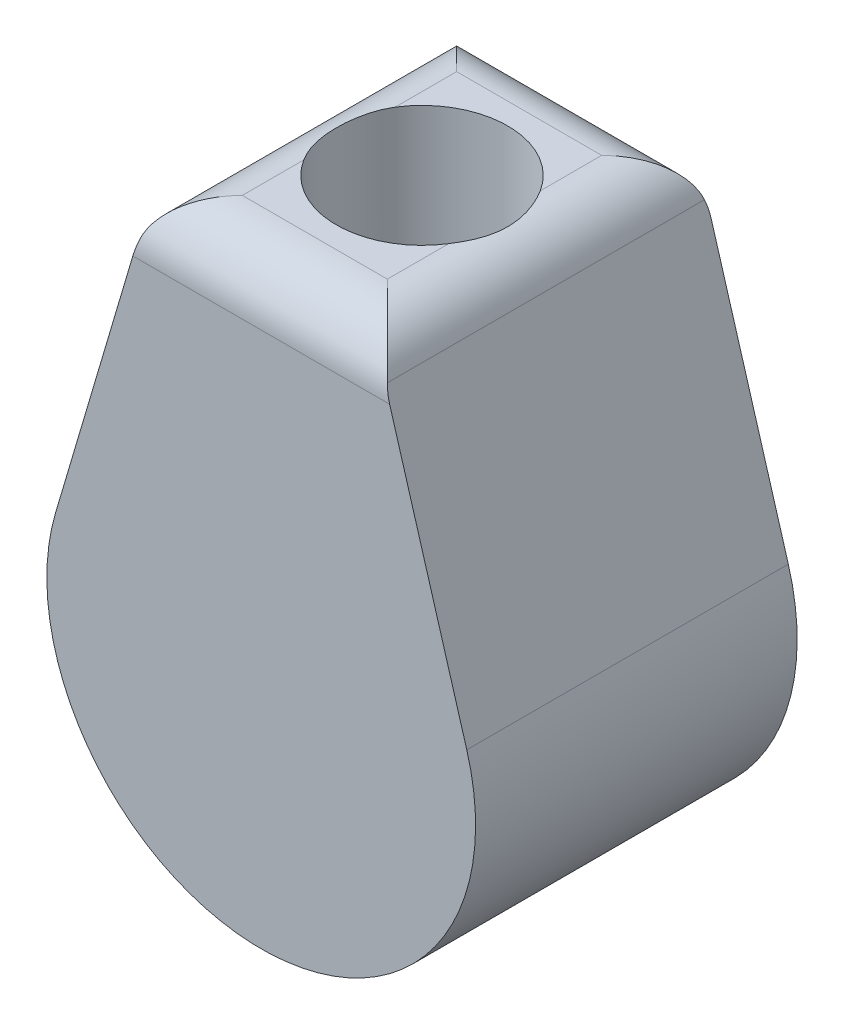
SolidWorks part; units mm, degrees
ref_plane "Front Plane" through (0, 0, 0) normal (0, 0, 1) x (1, 0, 0)
ref_plane "Top Plane" through (0, 0, 0) normal (0, 1, 0) x (1, 0, 0)
ref_plane "Right Plane" through (0, 0, 0) normal (1, 0, 0) x (0, 0, -1)
sketch "Sketch1" plane through (0, 0, 0) normal (0, 0, 1) x (1, 0, 0)
  line L0 (0, 0) -> (0, -5.625) construction
  line L1 (-1.6, 0) -> (-2.1, 0)
  line L2 (-2.1, 0) -> (-3.8356, -5.865)
  line L3 (-1.6, 0) -> (-1.6, -8)
  line L4 (-1.6, -8) -> (0, -8)
  line L5 (0, -8) -> (0, -10) construction
  line L6 (1.6, 0) -> (1.6, -8)
  line L7 (2.1, 0) -> (3.8356, -5.865)
  line L8 (1.6, 0) -> (2.1, 0)
  line L9 (0, -8) -> (1.6, -8)
  arc A0 (-3.8356, -5.865) -> (3.8356, -5.865) centre (0, -7) ccw
  point P20 (0, -11)
  dimension "D4" = 8
  dimension "D5" = 3
  dimension "D1" = 1.6
  dimension "D2" = 0.5
  dimension "D3" = 8
extrude "Boss-Extrude1" add sketch "Sketch1" along normal blind 6
sketch "Sketch2" plane through (0, -8, 0) normal (0, 1, 0) x (1, 0, 0)
  line L0 (0, -3) -> (-1.6, -3) construction
  line L1 (-1.6, -6) -> (-1.6, 0) construction
  line L2 (1.6, -6) -> (1.6, 0) construction
  line L7 (1.6, 0) -> (-1.6, 0)
  line L8 (-1.6, 0) -> (-1.6, -6)
  line L9 (-1.6, -6) -> (1.6, -6)
  line L10 (1.6, -6) -> (1.6, 0)
  line L11 (1.6, 0) -> (-1.6, 0)
  line L12 (-1.6, 0) -> (-1.6, -6)
  line L13 (-1.6, -6) -> (1.6, -6)
  line L14 (1.6, -6) -> (1.6, 0)
  circle A0 centre (0, -3) radius 1.6
  line M7 (1.6, 0) -> (-1.6, 0)
  line M8 (-1.6, 0) -> (-1.6, -6)
  line M9 (-1.6, -6) -> (1.6, -6)
  line M10 (1.6, -6) -> (1.6, 0)
  dimension "D1" = 0
extrude "Boss-Extrude2" add sketch "Sketch2" along direction (0, -1, 0) on the side of the normal up to surface (8 mm away) contours A0 L12 M9 M10 | A0 L14 M7 M8 region at (0, -8, 0.9083) region at (0, -8, 5.0917) up to face at (1.85, 0, 3)
fillet "Fillet1" radius 1 4 edges at (0, 0, 6) (2.1, 0, 3) (-2.1, 0, 3) (0, 0, 0)
